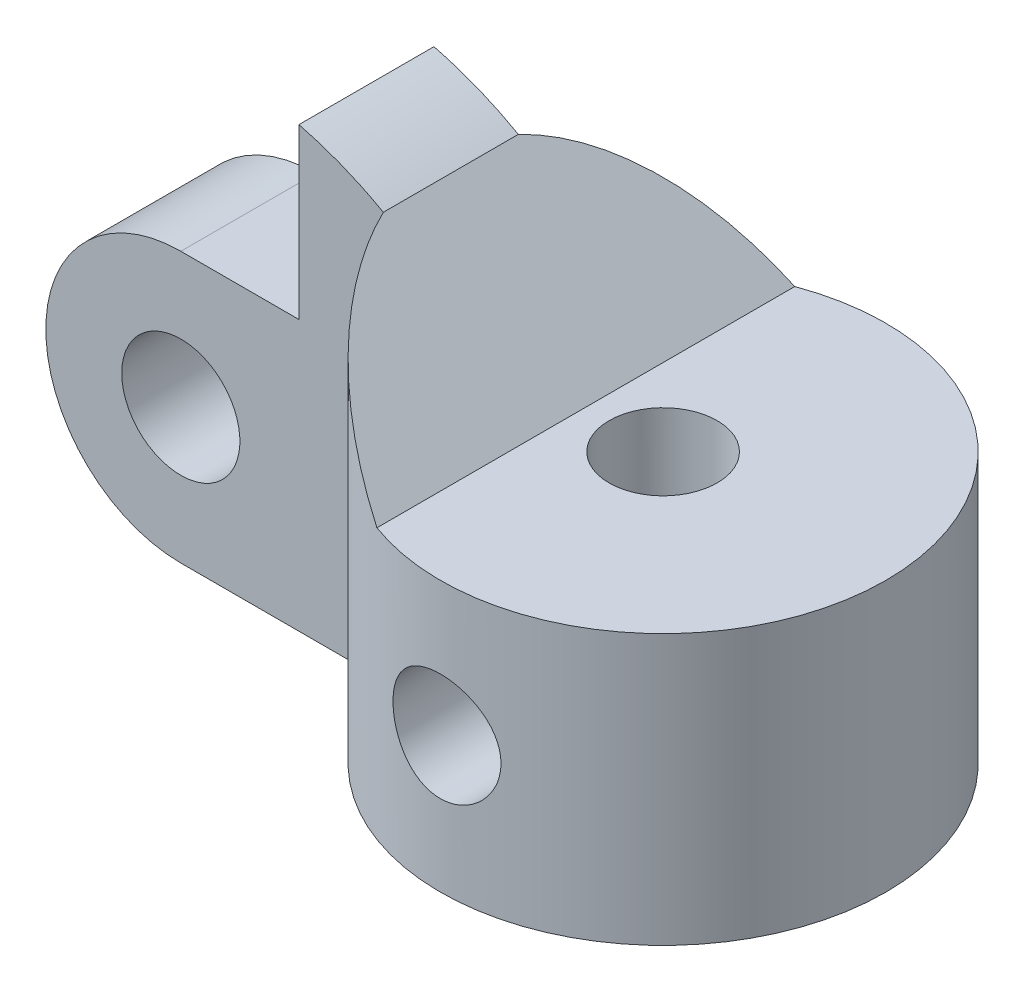
SolidWorks part; units mm, degrees
ref_plane "Front Plane" through (0, 0, 0) normal (0, 0, 1) x (1, 0, 0)
ref_plane "Top Plane" through (0, 0, 0) normal (0, 1, 0) x (1, 0, 0)
ref_plane "Right Plane" through (0, 0, 0) normal (1, 0, 0) x (0, 0, -1)
sketch "Sketch1" plane through (0, 0, 0) normal (0, 1, 0) x (1, 0, 0)
  line L0 (0, 0) -> (0, 8.3213) construction
  line L1 (-16.2897, 2) -> (-6.2897, 2)
  line L2 (-16.2897, 2) -> (-16.2897, -2)
  line L3 (-16.2897, -2) -> (-6.2897, -2)
  line L5 (0, 0) -> (-16.2897, 0) construction
  circle A0 centre (0, 0) radius 1.6
  arc A1 (-6.2897, -2) -> (6.2897, -2) centre (0, 0) ccw
  circle A2 centre (0, 0) radius 6.6 construction
  arc A3 (6.2897, 2) -> (-6.2897, 2) centre (0, 0) ccw
  arc A4 (-6.2897, -2) -> (-6.2897, 2) centre (0, 0) ccw
  dimension "D1" = 3.2
  dimension "D3" = 4
  dimension "D4" = 10
  dimension "D2" = 5
extrude "Boss-Extrude1" add sketch "Sketch1" along normal blind 8 contours A1 A4 A3 L1 L2 L3 A0 region at (-2.6567, 0, 0)
sketch "Sketch2" plane through (0, 0, 2) normal (0, 0, 1) x (1, 0, 0)
  line L0 (-16.2897, 4) -> (-12.2897, 4) construction
  line L3 (-16.2897, 8) -> (-16.2897, 0) construction
  line L6 (0, 0) -> (0, 10.8746) construction
  line L8 (-12.2897, 4) -> (0, 4) construction
  line L11 (-12.2897, 8) -> (-12.2897, 4) construction
  line L16 (-16.2897, 0) -> (-6.2897, 0)
  line L17 (-6.2897, 0) -> (-6.2897, 8)
  line L18 (-6.2897, 8) -> (-16.2897, 8)
  line L19 (-16.2897, 8) -> (-16.2897, 0)
  line L20 (-16.2897, 0) -> (-12.2897, 0)
  line L22 (-12.2897, 8) -> (-16.2897, 8)
  line L23 (-16.2897, 8) -> (-16.2897, 0)
  circle A0 centre (-12.2897, 4) radius 1.75
  circle A2 centre (0, 4) radius 1.6
  arc A3 (-12.2897, 8) -> (-12.2897, 0) centre (-12.2897, 4) ccw
  line M9 (-16.2897, 8) -> (-16.2897, 0)
  line M12 (-16.2897, 0) -> (-6.2897, 0)
  line M13 (-6.2897, 8) -> (-16.2897, 8)
  dimension "D1" = 3.5
  dimension "D2" = 3.2
  dimension "D3" = 0
extrude "Cut-Extrude1" cut sketch "Sketch2" against normal through all both and the other way through all contours A3 M13 M9 | A3 L23 M12 | A0 | A2 region at (-15.3962, 0.8935, 2) region at (-15.3962, 7.1065, 2) region at (-12.2897, 4, 2) region at (0, 4, 2)
sketch "Sketch3" plane through (0, 0, 2) normal (0, 0, 1) x (1, 0, 0)
  line L0 (-16.2897, 4) -> (-22.2897, 4)
  line L1 (-12.5769, 0) -> (-19.7182, 1.0308)
  line L2 (-12.2897, 0) -> (-6.2897, 0) construction
  arc A0 (-12.2897, 8) -> (-12.2897, 0) centre (-12.2897, 4) ccw construction
  arc A1 (-22.2897, 4) -> (-19.7182, 1.0308) centre (-19.2897, 4) ccw
  arc A2 (-16.2897, 4) -> (-12.2897, 0) centre (-12.2897, 4) ccw
  arc M5 (-12.2897, 8) -> (-12.2897, 0) centre (-12.2897, 4) ccw
  dimension "D1" = 3
extrude "Boss-Extrude2" [suppressed] add sketch "Sketch3" against normal up to surface (2 mm away) contours L0 A1 L1 M5 up to face at (-14.0397, 4, -2)
sketch "Sketch4" plane through (0, 8, 0) normal (0, 1, 0) x (1, 0, 0)
  line L0 (-12.2897, 2) -> (-6.2897, 2) construction
  line L1 (-8.7897, 2) -> (-6.2897, 2)
  line L2 (-8.7897, 2) -> (-8.7897, -2)
  line L3 (-8.7897, -2) -> (-6.2897, -2)
  line L4 (-6.2897, 2) -> (-6.2897, -2)
  line L6 (-12.2897, -2) -> (-6.2897, -2) construction
  point P8 (-8.2648, -2)
  point P10 (-6.2897, 2)
  dimension "D1" = 2.5
extrude "Boss-Extrude3" add sketch "Sketch4" along normal blind 5
chamfer "Chamfer1" distance 4 angle 45 1 edges at (-6.2897, 8, 0)
fillet "Fillet2" radius 10 1 edges at (-6.2897, 13, 0) first distance on face at (-6.2897, 12.5, 0)
